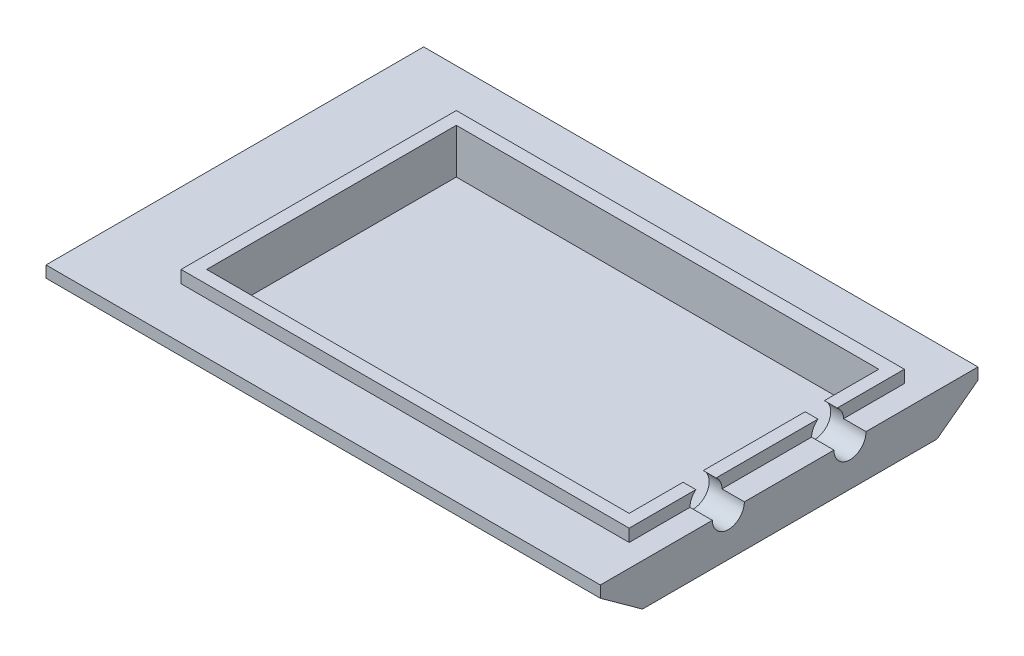
SolidWorks part; units mm, degrees
ref_plane "Front Plane" through (0, 0, 0) normal (0, 0, 1) x (1, 0, 0)
ref_plane "Top Plane" through (0, 0, 0) normal (0, 1, 0) x (1, 0, 0)
ref_plane "Right Plane" through (0, 0, 0) normal (1, 0, 0) x (0, 0, -1)
sketch "Sketch1" plane through (0, 0, 0) normal (0, 1, 0) x (1, 0, 0)
  line L1 (-190.5, 0) -> (0, 0)
  line L2 (-190.5, 0) -> (-190.5, -116.84)
  line L3 (-190.5, -116.84) -> (0, -116.84)
  line L4 (0, 0) -> (0, -116.84)
  dimension "D1" = 190.5
  dimension "D2" = 116.84
ref_plane "Plane1" through (0, 12.0904, 0) normal (0, 1, 0) x (1, 0, 0)
sketch "Sketch2" plane through (0, 12.0904, 0) normal (0, 1, 0) x (1, 0, 0)
  line L0 (0, -6.6497) -> (0, 6.6497) construction
  line L1 (-219.964, 16.2891) -> (0, 16.2891)
  line L2 (-219.964, 16.2891) -> (-219.964, -133.5709)
  line L3 (-219.964, -133.5709) -> (0, -133.5709)
  line L4 (0, 16.2891) -> (0, -133.5709)
  line L5 (-190.5, 0) -> (0, 0) construction
  dimension "D1" = 149.86
  dimension "D2" = 219.964
  dimension "D3" = 16.2891
loft "Loft1" add profiles "Sketch2", "Sketch1" connector at (-219.964, 12.0904, 133.5709) connector at (-190.5, 0, 116.84)
extrude "Boss-Extrude2" add sketch "Sketch2<2>" along normal blind 4.572
sketch "Sketch2<2>" plane through (0, 12.0904, 0) normal (0, 1, 0) x (1, 0, 0) same geometry as "Sketch2"
ref_plane "Plane2" through (0, 16.51, 0) normal (0, 1, 0) x (1, 0, 0)
sketch "Sketch3" plane through (0, 16.51, 0) normal (0, 1, 0) x (1, 0, 0)
  line L0 (0, -133.5709) -> (0, 16.2891) construction
  line L1 (-186.69, -4.0309) -> (-8.89, -4.0309)
  line L2 (-186.69, -4.0309) -> (-186.69, -113.2509)
  line L3 (-186.69, -113.2509) -> (-8.89, -113.2509)
  line L4 (-8.89, -4.0309) -> (-8.89, -113.2509)
  line L5 (-219.964, -133.5709) -> (0, -133.5709) construction
  dimension "D1" = 177.8
  dimension "D2" = 109.22
  dimension "D3" = 8.89
  dimension "D4" = 20.32
extrude "Boss-Extrude3" add sketch "Sketch3" along normal blind 5.08
sketch "Sketch4" plane through (0, 16.51, 0) normal (0, 1, 0) x (1, 0, 0)
  line L0 (-181.61, -9.1109) -> (-181.61, -108.1709)
  line L5 (-181.61, -108.1709) -> (-13.97, -108.1709)
  line L6 (-13.97, -9.1109) -> (-13.97, -108.1709)
  line L7 (-181.61, -9.1109) -> (-13.97, -9.1109)
  line L8 (-8.89, -113.2509) -> (-8.89, -4.0309) construction
  line L9 (-186.69, -4.0309) -> (-186.69, -113.2509) construction
  line L11 (-186.69, -4.0309) -> (-8.89, -4.0309) construction
  line L12 (-186.69, -113.2509) -> (-8.89, -113.2509) construction
  dimension "D1" = 5.08
  dimension "D2" = 5.08
  dimension "D3" = 5.08
  dimension "D4" = 5.08
extrude "Cut-Extrude1" cut sketch "Sketch4" along normal through all
extrude "Cut-Extrude2" cut sketch "Sketch4<2>" against normal blind 12.7
sketch "Sketch4<2>" plane through (0, 16.51, 0) normal (0, 1, 0) x (1, 0, 0) same geometry as "Sketch4"
sketch "Sketch5" plane through (0, 0, 0) normal (1, 0, 0) x (0, 0, -1)
  line L0 (-133.5709, 16.6624) -> (16.2891, 16.6624) construction
  line L1 (82.4231, 16.51) -> (-82.4231, 16.51) construction
  circle A0 centre (-82.7709, 16.6624) radius 6.35
  circle A1 centre (-34.5109, 16.51) radius 6.35
  dimension "D1" = 12.7
  dimension "D3" = 12.7
  dimension "D2" = 50.8
  dimension "D4" = 50.8
extrude "Cut-Extrude3" cut sketch "Sketch5" against normal blind 19.05
